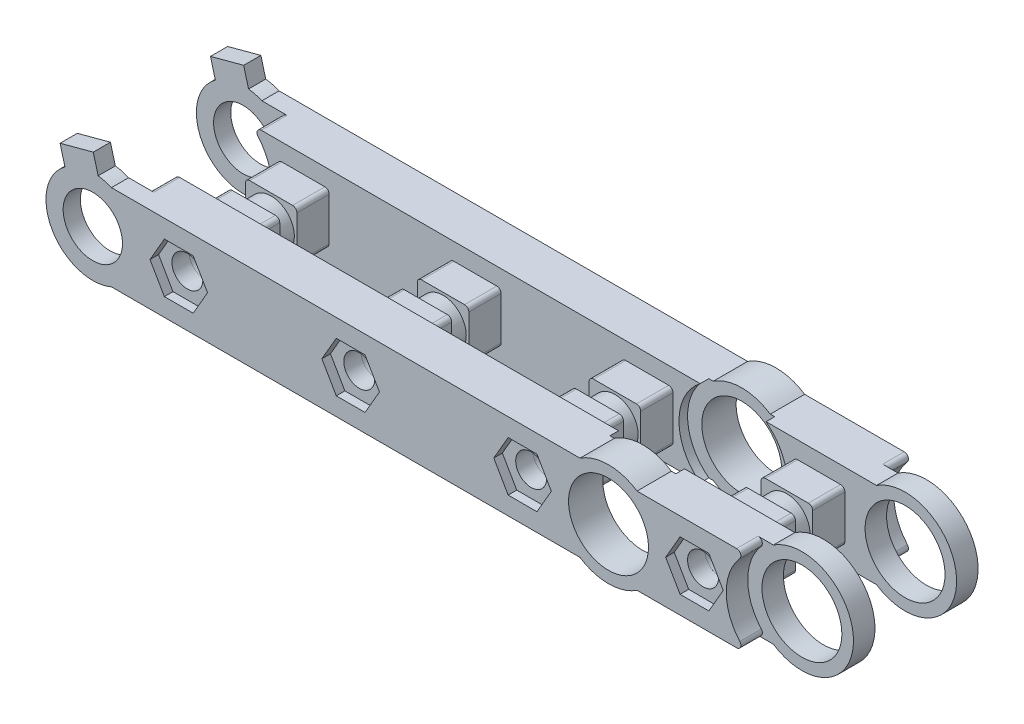
SolidWorks part; units mm, degrees
material "ABS"
ref_plane "正面" through (0, 0, 0) normal (0, 0, 1) x (1, 0, 0)
ref_plane "平面" through (0, 0, 0) normal (0, 1, 0) x (1, 0, 0)
ref_plane "右側面" through (0, 0, 0) normal (1, 0, 0) x (0, 0, -1)
sketch "ｽｹｯﾁ1" plane through (0, 0, 0) normal (0, 0, 1) x (1, 0, 0)
  line L0 (0, 0) -> (-20, 0) construction
  line L1 (3.64, -3.64) -> (-3.64, -3.64) construction
  line L2 (3.64, -3.64) -> (3.64, 3.64) construction
  line L3 (3.64, 3.64) -> (-3.64, 3.64) construction
  line L4 (-3.64, -3.64) -> (-3.64, 3.64) construction
  line L5 (3.64, -3.64) -> (-3.64, 3.64) construction
  line L6 (3.64, 3.64) -> (-3.64, -3.64) construction
  line L7 (-20, 0) -> (-40, 0) construction
  line L8 (-40, 0) -> (-60, 0) construction
  line L9 (-60, 0) -> (-80, 0) construction
  line L10 (-80, 0) -> (-100, 0) construction
  line L11 (0, 5) -> (-20, 5) construction
  line L18 (-20, 5) -> (-40, 5) construction
  line L19 (-40, 5) -> (-60, 5) construction
  line L20 (-60, 5) -> (-77.8315, 5) construction
  line L21 (-80, 5) -> (-100, 5) construction
  line L22 (0, -5) -> (-20, -5) construction
  line L23 (-20, -5) -> (-40, -5) construction
  line L24 (-40, -5) -> (-60, -5) construction
  line L25 (-60, -5) -> (-77.8315, -5) construction
  line L26 (-80, -5) -> (-100, -5) construction
  line L27 (-102.1685, 5) -> (-80, 5) construction
  line L28 (-77.8315, 5) -> (-60, 5)
  line L29 (-60, 5) -> (-40, 5)
  line L30 (-40, 5) -> (-20, 5)
  line L31 (-20, 5) -> (-3.3166, 5)
  line L32 (-3.3166, -5) -> (-20, -5)
  line L33 (-20, -5) -> (-40, -5)
  line L34 (-40, -5) -> (-60, -5)
  line L35 (-60, -5) -> (-77.8315, -5)
  line L36 (-80, -5) -> (-102.1685, -5) construction
  line L39 (-60, 5) -> (-80, 5) construction
  line L40 (-60, -5) -> (-80, -5) construction
  line L41 (-80, 5) -> (-77.8315, 5) construction
  line L42 (-80, -5) -> (-77.8315, -5) construction
  circle A0 centre (-10, 0) radius 1.8
  circle A1 centre (-30, 0) radius 1.8
  circle A2 centre (-50, 0) radius 1.8
  circle A3 centre (-70, 0) radius 1.8
  circle A4 centre (-90, 0) radius 1.8 construction
  circle A5 centre (-100, 0) radius 3.45 construction
  arc A6 (-3.3166, -5) -> (-3.3166, 5) centre (0, 0) ccw
  arc A7 (-102.1685, 5) -> (-102.1685, -5) centre (-100, 0) ccw construction
  circle A8 centre (0, 0) radius 4.39
  circle A9 centre (-80, 0) radius 3.45
  arc A11 (-77.8315, 5) -> (-77.8315, -5) centre (-80, 0) ccw
  point P0 (0, 0)
  dimension "D8" = 3.6
  dimension "D9" = 6.9
  dimension "D10" = 12
  dimension "D13" = 10.9
  dimension "D3" = 8.78
  dimension "D4" = 6.9
  dimension "D5" = 10.9
  dimension "D1" = 7.28
  dimension "D2" = 7.28
  dimension "D7" = 20
  dimension "D11" = 5
  dimension "D12" = 5
extrude "ﾎﾞｽ - 押し出し1" add sketch "ｽｹｯﾁ1" along normal blind 2
sketch "ｽｹｯﾁ2" plane through (0, 0, 0) normal (0, 0, -1) x (-1, 0, 0)
  line L19 (77.8315, 5) -> (60, 5)
  line L20 (60, 5) -> (40, 5)
  line L21 (40, 5) -> (20, 5)
  line L22 (20, 5) -> (3.3166, 5)
  line L23 (3.3166, -5) -> (20, -5)
  line L24 (20, -5) -> (40, -5)
  line L25 (40, -5) -> (60, -5)
  line L26 (60, -5) -> (77.8315, -5)
  line L29 (74.902, 5) -> (60, 5)
  line L30 (60, 5) -> (40, 5)
  line L31 (40, 5) -> (20, 5)
  line L32 (20, 5) -> (3.3166, 5)
  line L33 (3.3166, -5) -> (20, -5)
  line L34 (20, -5) -> (40, -5)
  line L35 (40, -5) -> (60, -5)
  line L36 (60, -5) -> (74.902, -5)
  circle A1 centre (30, 0) radius 1.8
  circle A2 centre (30, 0) radius 1.8
  circle A3 centre (10, 0) radius 1.8
  circle A4 centre (10, 0) radius 1.8
  arc A7 (75.2768, 4.1691) -> (75.2768, -4.1691) centre (80, 0) ccw
  circle A9 centre (70, 0) radius 1.8
  circle A10 centre (70, 0) radius 1.8
  circle A11 centre (50, 0) radius 1.8
  circle A12 centre (50, 0) radius 1.8
  arc A14 (3.3166, 5) -> (3.3166, -5) centre (0, 0) ccw
  arc A16 (3.3166, 5) -> (3.3166, -5) centre (0, 0) ccw
  circle A18 centre (0, 0) radius 4.39 construction
  circle A19 centre (0, 0) radius 4.39
  arc A20 (75.2768, -4.1691) -> (74.902, -5) centre (74.902, -4.5) cw
  arc A21 (75.2768, 4.1691) -> (74.902, 5) centre (74.902, 4.5) ccw
  arc A22 (77.8315, -5) -> (77.8315, 5) centre (80, 0) ccw
  dimension "D4" = 0.5
  dimension "D3" = 6.3
  dimension "D1" = 0
  dimension "D2" = 0
  dimension "D6" = 0
  dimension "D7" = 0
  dimension "D8" = 0
extrude "ﾎﾞｽ - 押し出し2" add sketch "ｽｹｯﾁ2" along normal blind 3
ref_plane "平面1" through (0, 0, -17.5) normal (0, 0, 1) x (1, 0, 0)
ref_plane "平面2" through (0, 0, -7.75) normal (0, 0, 1) x (1, 0, 0)
sketch "ｽｹｯﾁ3" plane through (0, 0, 2) normal (0, 0, 1) x (1, 0, 0)
  line L0 (-80, 0) -> (-80, 5.45) construction
  line L2 (-80, 0) -> (-81.4106, 5.2643) construction
  line L3 (-79.9446, 7.5206) -> (-79.0128, 4.0433)
  line L4 (-79.9446, 7.5206) -> (-83.8083, 6.4853)
  line L5 (-79.0128, 4.0433) -> (-82.8765, 3.008)
  line L6 (-83.8083, 6.4853) -> (-82.8765, 3.008)
  line L7 (-79.9446, 7.5206) -> (-82.8765, 3.008) construction
  line L8 (-79.0128, 4.0433) -> (-83.8083, 6.4853) construction
  arc A1 (-77.8315, 5) -> (-77.8315, -5) centre (-80, 0) ccw construction
  dimension "D1" = 1.8
  dimension "D2" = 4
  dimension "D3" = 15
extrude "ﾎﾞｽ - 押し出し3" add sketch "ｽｹｯﾁ3" against normal up to surface (2 mm away) up to face at (-76.55, 0, 0)
sketch "ｽｹｯﾁ4" plane through (0, 0, -17.5) normal (0, 0, 1) x (1, 0, 0)
  line L19 (-60, 5) -> (-77.8315, 5)
  line L20 (-40, 5) -> (-60, 5)
  line L21 (-20, 5) -> (-40, 5)
  line L22 (-3.3166, 5) -> (-20, 5)
  line L23 (-20, -5) -> (-3.3166, -5)
  line L24 (-40, -5) -> (-20, -5)
  line L25 (-60, -5) -> (-40, -5)
  line L26 (-77.8315, -5) -> (-60, -5)
  line L29 (-60, 5) -> (-77.8315, 5)
  line L30 (-40, 5) -> (-60, 5)
  line L31 (-20, 5) -> (-40, 5)
  line L32 (-3.3166, 5) -> (-20, 5)
  line L33 (-20, -5) -> (-3.3166, -5)
  line L34 (-40, -5) -> (-20, -5)
  line L35 (-60, -5) -> (-40, -5)
  line L36 (-77.8315, -5) -> (-60, -5)
  circle A0 centre (0, 0) radius 4.39 construction
  circle A1 centre (-30, 0) radius 1.8
  circle A2 centre (-30, 0) radius 1.8
  circle A3 centre (-10, 0) radius 1.8
  circle A4 centre (-10, 0) radius 1.8
  circle A5 centre (-80, 0) radius 3.45 construction
  circle A7 centre (-80, 0) radius 3.45
  circle A9 centre (-70, 0) radius 1.8
  circle A10 centre (-70, 0) radius 1.8
  circle A11 centre (-50, 0) radius 1.8
  circle A12 centre (-50, 0) radius 1.8
  circle A13 centre (0, 0) radius 4.39
  arc A14 (-3.3166, -5) -> (-3.3166, 5) centre (0, 0) ccw
  arc A15 (-77.8315, 5) -> (-77.8315, -5) centre (-80, 0) ccw
  arc A16 (-3.3166, -5) -> (-3.3166, 5) centre (0, 0) ccw
  arc A21 (-77.8315, 5) -> (-77.8315, -5) centre (-80, 0) ccw
  dimension "D1" = 0
  dimension "D2" = 0
  dimension "D6" = 0
  dimension "D7" = 0
  dimension "D8" = 0
extrude "ﾎﾞｽ - 押し出し4" add sketch "ｽｹｯﾁ4" along normal blind 2 separate body
sketch "ｽｹｯﾁ5" plane through (0, 0, -15.5) normal (0, 0, 1) x (1, 0, 0)
  line L18 (-74.902, -5) -> (-60, -5)
  line L19 (-60, -5) -> (-40, -5)
  line L20 (-40, -5) -> (-20, -5)
  line L21 (-20, -5) -> (-3.3166, -5)
  line L22 (-3.3166, 5) -> (-20, 5)
  line L23 (-20, 5) -> (-40, 5)
  line L24 (-40, 5) -> (-60, 5)
  line L25 (-60, 5) -> (-74.902, 5)
  line L28 (-74.902, -5) -> (-60, -5)
  line L29 (-60, -5) -> (-40, -5)
  line L30 (-40, -5) -> (-20, -5)
  line L31 (-20, -5) -> (-3.3166, -5)
  line L32 (-3.3166, 5) -> (-20, 5)
  line L33 (-20, 5) -> (-40, 5)
  line L34 (-40, 5) -> (-60, 5)
  line L35 (-60, 5) -> (-74.902, 5)
  circle A0 centre (0, 0) radius 4.39 construction
  circle A1 centre (-10, 0) radius 1.8
  circle A2 centre (-10, 0) radius 1.8
  circle A3 centre (-30, 0) radius 1.8
  circle A4 centre (-30, 0) radius 1.8
  circle A5 centre (-50, 0) radius 1.8
  circle A6 centre (-50, 0) radius 1.8
  circle A7 centre (-70, 0) radius 1.8
  circle A8 centre (-70, 0) radius 1.8
  circle A11 centre (0, 0) radius 4.39
  arc A12 (-3.3166, -5) -> (-3.3166, 5) centre (0, 0) ccw
  arc A14 (-3.3166, -5) -> (-3.3166, 5) centre (0, 0) ccw
  arc A20 (-75.2768, -4.1691) -> (-74.902, -5) centre (-74.902, -4.5) ccw
  arc A22 (-75.2768, -4.1691) -> (-74.902, -5) centre (-74.902, -4.5) ccw
  arc A23 (-75.2768, -4.1691) -> (-75.2768, 4.1691) centre (-80, 0) ccw
  arc A24 (-75.2768, -4.1691) -> (-75.2768, 4.1691) centre (-80, 0) ccw
  arc A25 (-74.902, 5) -> (-75.2768, 4.1691) centre (-74.902, 4.5) ccw
  arc A26 (-74.902, 5) -> (-75.2768, 4.1691) centre (-74.902, 4.5) ccw
  dimension "D1" = 0
  dimension "D2" = 0
  dimension "D4" = 0
  dimension "D5" = 0
  dimension "D7" = 0
extrude "ﾎﾞｽ - 押し出し5" add sketch "ｽｹｯﾁ5" along normal blind 3
sketch "ｽｹｯﾁ12" plane through (0, 0, 2) normal (0, 0, 1) x (1, 0, 0)
  circle A0 centre (0, 0) radius 6.3
  dimension "D1" = 12.6
extrude "ｶｯﾄ - 押し出し5" cut sketch "ｽｹｯﾁ12" against normal blind 2.5
sketch "ｽｹｯﾁ14" plane through (0, 0, -3) normal (0, 0, -1) x (-1, 0, 0)
  circle A1 centre (0, 0) radius 6.3
  circle A2 centre (0, 0) radius 6.3
  dimension "D1" = 0
extrude "ｶｯﾄ - 押し出し7" cut sketch "ｽｹｯﾁ14" against normal blind 1
fillet "ﾌｨﾚｯﾄ1" radius 0.5 4 edges at (-3.8328, -5, 0.75) (-3.8328, -5, -2.5) (-3.8328, 5, -2.5) (-3.8328, 5, 0.75)
sketch "ｽｹｯﾁ15" plane through (0, 0, -17.5) normal (0, 0, -1) x (-1, 0, 0)
  circle A1 centre (0, 0) radius 6.3
  circle A2 centre (0, 0) radius 6.3
  dimension "D1" = 0
extrude "ｶｯﾄ - 押し出し8" cut sketch "ｽｹｯﾁ15" against normal blind 2.5
sketch "ｽｹｯﾁ16" plane through (0, 0, -12.5) normal (0, 0, 1) x (1, 0, 0)
  circle A1 centre (0, 0) radius 6.3
  circle A2 centre (0, 0) radius 6.3
  dimension "D1" = 0
extrude "ｶｯﾄ - 押し出し9" cut sketch "ｽｹｯﾁ16" against normal blind 1
fillet "ﾌｨﾚｯﾄ2" radius 0.5 4 edges at (-3.8328, -5, -16.25) (-3.8328, -5, -13) (-3.8328, 5, -16.25) (-3.8328, 5, -13)
sketch "ｽｹｯﾁ6" plane through (0, 0, -17.5) normal (0, 0, -1) x (-1, 0, 0)
  line L4 (79.9446, 7.5206) -> (79.0128, 4.0433)
  line L5 (79.0128, 4.0433) -> (82.8765, 3.008)
  line L6 (82.8765, 3.008) -> (83.8083, 6.4853)
  line L7 (83.8083, 6.4853) -> (79.9446, 7.5206)
  line L8 (79.9446, 7.5206) -> (79.0128, 4.0433)
  line L9 (79.0128, 4.0433) -> (82.8765, 3.008)
  line L10 (82.8765, 3.008) -> (83.8083, 6.4853)
  line L11 (83.8083, 6.4853) -> (79.9446, 7.5206)
  dimension "D1" = 0
extrude "ﾎﾞｽ - 押し出し6" add sketch "ｽｹｯﾁ6" against normal up to surface (2 mm away) up to face at (-77.0998, 0, -15.5)
sketch "ｽｹｯﾁ7" plane through (0, 0, -3) normal (0, 0, -1) x (-1, 0, 0)
  line L0 (26.9, -3.1) -> (26.9, 3.1)
  line L1 (6.9, -3.1) -> (13.1, -3.1)
  line L2 (6.9, -3.1) -> (6.9, 3.1)
  line L3 (6.9, 3.1) -> (13.1, 3.1)
  line L4 (13.1, -3.1) -> (13.1, 3.1)
  line L5 (6.9, -3.1) -> (13.1, 3.1) construction
  line L6 (6.9, 3.1) -> (13.1, -3.1) construction
  line L7 (26.9, -3.1) -> (33.1, -3.1)
  line L8 (26.9, 3.1) -> (33.1, 3.1)
  line L9 (33.1, -3.1) -> (33.1, 3.1)
  line L10 (26.9, -3.1) -> (33.1, 3.1) construction
  line L11 (26.9, 3.1) -> (33.1, -3.1) construction
  line L12 (46.9, -3.1) -> (46.9, 3.1)
  line L13 (46.9, -3.1) -> (53.1, -3.1)
  line L14 (46.9, 3.1) -> (53.1, 3.1)
  line L15 (53.1, -3.1) -> (53.1, 3.1)
  line L16 (46.9, -3.1) -> (53.1, 3.1) construction
  line L17 (46.9, 3.1) -> (53.1, -3.1) construction
  line L18 (66.9, -3.1) -> (66.9, 3.1)
  line L19 (66.9, -3.1) -> (73.1, -3.1)
  line L20 (66.9, 3.1) -> (73.1, 3.1)
  line L21 (73.1, -3.1) -> (73.1, 3.1)
  line L22 (66.9, -3.1) -> (73.1, 3.1) construction
  line L23 (66.9, 3.1) -> (73.1, -3.1) construction
  line L30 (5.098, 5) -> (77.8315, 5) construction
  line L31 (5.098, 5) -> (77.8315, 5) construction
  line L32 (5.098, 5) -> (77.8315, 5) construction
  circle A0 centre (30, 0) radius 1.8 construction
  circle A1 centre (50, 0) radius 1.8 construction
  circle A2 centre (70, 0) radius 1.8 construction
  point P0 (10, 0)
  point P7 (30, 0)
  point P8 (50, 0)
  point P9 (70, 0)
  dimension "D1" = 6.2
  dimension "D2" = 6.2
extrude "ｶｯﾄ - 押し出し1" cut sketch "ｽｹｯﾁ7" against normal blind 2
sketch "ｽｹｯﾁ8" plane through (0, 0, -12.5) normal (0, 0, 1) x (1, 0, 0)
  line L0 (-13, -3) -> (-7, -3)
  line L1 (-7, -3) -> (-7, 3)
  line L2 (-7, 3) -> (-13, 3)
  line L3 (-13, 3) -> (-13, -3)
  line L4 (-13.1, -3.1) -> (-6.9, -3.1)
  line L5 (-13.1, 3.1) -> (-13.1, -3.1)
  line L6 (-6.9, 3.1) -> (-13.1, 3.1)
  line L7 (-6.9, -3.1) -> (-6.9, 3.1)
  line L8 (-13.1, -3.1) -> (-6.9, -3.1) construction
  line L9 (-13.1, 3.1) -> (-13.1, -3.1) construction
  line L10 (-6.9, 3.1) -> (-13.1, 3.1) construction
  line L11 (-6.9, -3.1) -> (-6.9, 3.1) construction
  line L12 (-26.9, -3.1) -> (-26.9, 3.1)
  line L13 (-26.9, 3.1) -> (-33.1, 3.1)
  line L14 (-33.1, 3.1) -> (-33.1, -3.1)
  line L15 (-33.1, -3.1) -> (-26.9, -3.1)
  line L16 (-26.9, -3.1) -> (-26.9, 3.1) construction
  line L17 (-26.9, 3.1) -> (-33.1, 3.1) construction
  line L18 (-33.1, 3.1) -> (-33.1, -3.1) construction
  line L19 (-33.1, -3.1) -> (-26.9, -3.1) construction
  line L28 (-66.9, -3.1) -> (-66.9, 3.1)
  line L29 (-66.9, 3.1) -> (-73.1, 3.1)
  line L30 (-73.1, 3.1) -> (-73.1, -3.1)
  line L31 (-73.1, -3.1) -> (-66.9, -3.1)
  line L32 (-66.9, -3.1) -> (-66.9, 3.1) construction
  line L33 (-66.9, 3.1) -> (-73.1, 3.1) construction
  line L34 (-73.1, 3.1) -> (-73.1, -3.1) construction
  line L35 (-73.1, -3.1) -> (-66.9, -3.1) construction
  line L36 (-46.9, -3.1) -> (-46.9, 3.1)
  line L37 (-53.1, -3.1) -> (-46.9, -3.1)
  line L38 (-53.1, 3.1) -> (-53.1, -3.1)
  line L39 (-46.9, 3.1) -> (-53.1, 3.1)
  line L40 (-46.9, -3.1) -> (-46.9, 3.1) construction
  line L41 (-53.1, -3.1) -> (-46.9, -3.1) construction
  line L42 (-53.1, 3.1) -> (-53.1, -3.1) construction
  line L43 (-46.9, 3.1) -> (-53.1, 3.1) construction
  line L44 (-27, -3) -> (-27, 3)
  line L45 (-27, 3) -> (-33, 3)
  line L46 (-33, 3) -> (-33, -3)
  line L47 (-33, -3) -> (-27, -3)
  line L52 (-67, -3) -> (-67, 3)
  line L53 (-67, 3) -> (-73, 3)
  line L54 (-73, 3) -> (-73, -3)
  line L55 (-73, -3) -> (-67, -3)
  line L56 (-47, -3) -> (-47, 3)
  line L57 (-47, 3) -> (-53, 3)
  line L58 (-53, 3) -> (-53, -3)
  line L59 (-53, -3) -> (-47, -3)
  circle A1 centre (-70, 0) radius 1.8 construction
  circle A2 centre (-50, 0) radius 1.8 construction
  circle A3 centre (-30, 0) radius 1.8 construction
  circle A4 centre (-10, 0) radius 1.8 construction
  circle A6 centre (-70, 0) radius 1.8
  circle A7 centre (-50, 0) radius 1.8
  circle A8 centre (-30, 0) radius 1.8
  circle A9 centre (-10, 0) radius 1.8
  dimension "D1" = 0
  dimension "D2" = 0
  dimension "D4" = 0
  dimension "D5" = 0
  dimension "D6" = 0.1
extrude "ﾎﾞｽ - 押し出し7" add sketch "ｽｹｯﾁ8" along normal up to surface (11.5 mm away) up to face at (-8.2, 0, -1)
sketch "ｽｹｯﾁ9" plane through (0, 0, -7.75) normal (0, 0, 1) x (1, 0, 0)
  line L12 (-27, -3) -> (-27, 3)
  line L13 (-27, 3) -> (-33, 3)
  line L14 (-33, 3) -> (-33, -3)
  line L15 (-33, -3) -> (-27, -3)
  line L16 (-27, -3) -> (-27, 3)
  line L17 (-27, 3) -> (-33, 3)
  line L18 (-33, 3) -> (-33, -3)
  line L19 (-33, -3) -> (-27, -3)
  line L20 (-13, -3) -> (-7, -3)
  line L21 (-7, -3) -> (-7, 3)
  line L22 (-7, 3) -> (-13, 3)
  line L23 (-13, 3) -> (-13, -3)
  line L24 (-13, -3) -> (-7, -3)
  line L25 (-7, -3) -> (-7, 3)
  line L26 (-7, 3) -> (-13, 3)
  line L27 (-13, 3) -> (-13, -3)
  line L28 (-47, -3) -> (-47, 3)
  line L29 (-47, 3) -> (-53, 3)
  line L30 (-53, 3) -> (-53, -3)
  line L31 (-53, -3) -> (-47, -3)
  line L32 (-47, -3) -> (-47, 3)
  line L33 (-47, 3) -> (-53, 3)
  line L34 (-53, 3) -> (-53, -3)
  line L35 (-53, -3) -> (-47, -3)
  line L36 (-67, -3) -> (-67, 3)
  line L37 (-67, 3) -> (-73, 3)
  line L38 (-73, 3) -> (-73, -3)
  line L39 (-73, -3) -> (-67, -3)
  line L40 (-67, -3) -> (-67, 3)
  line L41 (-67, 3) -> (-73, 3)
  line L42 (-73, 3) -> (-73, -3)
  line L43 (-73, -3) -> (-67, -3)
  circle A1 centre (-70, 0) radius 2.7
  circle A3 centre (-50, 0) radius 2.7
  circle A5 centre (-30, 0) radius 2.7
  circle A7 centre (-10, 0) radius 2.7
  dimension "D6" = 5.4
  dimension "D2" = 0
  dimension "D3" = 0
  dimension "D4" = 0
  dimension "D5" = 0
extrude "ｶｯﾄ - 押し出し2" cut sketch "ｽｹｯﾁ9" against normal blind 1 and the other way blind 1
sketch "ｽｹｯﾁ10" plane through (0, 0, 2) normal (0, 0, 1) x (1, 0, 0)
  line L1 (-11.6743, 2.9) -> (-13.3486, 0)
  line L2 (-13.3486, 0) -> (-11.6743, -2.9)
  line L3 (-11.6743, -2.9) -> (-8.3257, -2.9)
  line L4 (-8.3257, -2.9) -> (-6.6514, 0)
  line L5 (-6.6514, 0) -> (-8.3257, 2.9)
  line L6 (-8.3257, 2.9) -> (-11.6743, 2.9)
  line L33 (-31.6743, -2.9) -> (-28.3257, -2.9)
  line L34 (-28.3257, -2.9) -> (-26.6514, 0)
  line L35 (-26.6514, 0) -> (-28.3257, 2.9)
  line L36 (-28.3257, 2.9) -> (-31.6743, 2.9)
  line L37 (-31.6743, 2.9) -> (-33.3486, 0)
  line L38 (-33.3486, 0) -> (-31.6743, -2.9)
  line L39 (-51.6743, -2.9) -> (-48.3257, -2.9)
  line L40 (-48.3257, -2.9) -> (-46.6514, 0)
  line L41 (-46.6514, 0) -> (-48.3257, 2.9)
  line L42 (-48.3257, 2.9) -> (-51.6743, 2.9)
  line L43 (-51.6743, 2.9) -> (-53.3486, 0)
  line L44 (-53.3486, 0) -> (-51.6743, -2.9)
  line L45 (-68.3257, -2.9) -> (-66.6514, 0)
  line L46 (-66.6514, 0) -> (-68.3257, 2.9)
  line L47 (-68.3257, 2.9) -> (-71.6743, 2.9)
  line L48 (-71.6743, 2.9) -> (-73.3486, 0)
  line L49 (-73.3486, 0) -> (-71.6743, -2.9)
  line L50 (-71.6743, -2.9) -> (-68.3257, -2.9)
  circle A0 centre (-10, 0) radius 2.9 construction
  circle A1 centre (-30, 0) radius 2.9 construction
  circle A2 centre (-50, 0) radius 2.9 construction
  circle A3 centre (-70, 0) radius 2.9 construction
  dimension "D1" = 5.8
extrude "ｶｯﾄ - 押し出し3" cut sketch "ｽｹｯﾁ10" against normal blind 1
sketch "ｽｹｯﾁ11" plane through (0, 0, -17.5) normal (0, 0, -1) x (-1, 0, 0)
  circle A0 centre (10, 0) radius 3.25
  circle A1 centre (30, 0) radius 3.25
  circle A2 centre (50, 0) radius 3.25
  circle A3 centre (70, 0) radius 3.25
  dimension "D1" = 6.5
extrude "ｶｯﾄ - 押し出し4" cut sketch "ｽｹｯﾁ11" against normal blind 1.5
sketch "ｽｹｯﾁ17" plane through (0, 0, 2) normal (0, 0, 1) x (1, 0, 0)
  line L0 (-30, 0) -> (-10, 0) construction
  circle A0 centre (-20, 0) radius 4.65
  dimension "D1" = 9.3
extrude "ｶｯﾄ - 押し出し10" cut sketch "ｽｹｯﾁ17" against normal through all
sketch "ｽｹｯﾁ18" plane through (0, 0, -3) normal (0, 0, -1) x (-1, 0, 0)
  circle A0 centre (20, 0) radius 6.3
  dimension "D1" = 12.6
extrude "ｶｯﾄ - 押し出し11" cut sketch "ｽｹｯﾁ18" against normal blind 1
sketch "ｽｹｯﾁ19" plane through (0, 0, -12.5) normal (0, 0, 1) x (1, 0, 0)
  circle A1 centre (-20, 0) radius 6.3
  circle A2 centre (-20, 0) radius 6.3
  dimension "D1" = 0
extrude "ｶｯﾄ - 押し出し12" cut sketch "ｽｹｯﾁ19" against normal blind 1
sketch "ｽｹｯﾁ20" plane through (0, 0, -13.5) normal (0, 0, 1) x (1, 0, 0)
  line L0 (-23.3166, 5) -> (-16.6834, 5)
  line L1 (-5.098, 5) -> (-77.8315, 5) construction
  line L2 (-23.3166, -5) -> (-16.6834, -5)
  line L3 (-77.8315, -5) -> (-5.098, -5) construction
  arc A0 (-23.3166, -5) -> (-16.6834, -5) centre (-20, 0) ccw
  arc A1 (-16.6834, 5) -> (-23.3166, 5) centre (-20, 0) ccw
  dimension "D1" = 12
extrude "ﾎﾞｽ - 押し出し8" add sketch "ｽｹｯﾁ20" against normal up to surface (4 mm away) up to face at (-15.35, 0, -17.5)
sketch "ｽｹｯﾁ21" plane through (0, 0, -2) normal (0, 0, -1) x (-1, 0, 0)
  line L1 (23.3166, -5) -> (16.6834, -5)
  line L2 (23.3166, -5) -> (16.6834, -5)
  line L3 (16.6834, 5) -> (23.3166, 5)
  line L4 (16.6834, 5) -> (23.3166, 5)
  arc A1 (16.6834, -5) -> (23.3166, -5) centre (20, 0) ccw
  arc A2 (16.6834, -5) -> (23.3166, -5) centre (20, 0) ccw
  arc A3 (23.3166, 5) -> (16.6834, 5) centre (20, 0) ccw
  arc A4 (23.3166, 5) -> (16.6834, 5) centre (20, 0) ccw
  dimension "D1" = 0
  dimension "D2" = 0
extrude "ﾎﾞｽ - 押し出し9" add sketch "ｽｹｯﾁ21" against normal up to surface (4 mm away) up to face at (-15.35, 0, 2)
sketch "ｽｹｯﾁ22" plane through (0, 0, -2) normal (0, 0, -1) x (-1, 0, 0)
  line L2 (5.098, 5) -> (3.3166, 5)
  line L3 (3.3166, -5) -> (5.098, -5)
  line L4 (5.098, 5) -> (3.3166, 5)
  line L5 (3.3166, -5) -> (5.098, -5)
  circle A0 centre (0, 0) radius 4.39 construction
  circle A1 centre (0, 0) radius 4.39
  arc A4 (3.3166, 5) -> (3.3166, -5) centre (0, 0) ccw
  arc A5 (4.7232, -4.1691) -> (5.098, -5) centre (5.098, -4.5) ccw
  arc A6 (4.7232, -4.1691) -> (4.7232, 4.1691) centre (0, 0) ccw
  arc A7 (5.098, 5) -> (4.7232, 4.1691) centre (5.098, 4.5) ccw
  arc A8 (3.3166, 5) -> (3.3166, -5) centre (0, 0) ccw
  arc A9 (4.7232, -4.1691) -> (5.098, -5) centre (5.098, -4.5) ccw
  arc A10 (4.7232, -4.1691) -> (4.7232, 4.1691) centre (0, 0) ccw
  arc A11 (5.098, 5) -> (4.7232, 4.1691) centre (5.098, 4.5) ccw
  dimension "D1" = 0
extrude "ﾎﾞｽ - 押し出し10" add sketch "ｽｹｯﾁ22" along normal up to surface (1 mm away) up to face at (-10, 0, -3)
sketch "ｽｹｯﾁ23" plane through (0, 0, -13.5) normal (0, 0, 1) x (1, 0, 0)
  line L2 (-3.3166, 5) -> (-5.098, 5)
  line L3 (-5.098, -5) -> (-3.3166, -5)
  line L4 (-3.3166, 5) -> (-5.098, 5)
  line L5 (-5.098, -5) -> (-3.3166, -5)
  circle A1 centre (0, 0) radius 4.39
  circle A2 centre (0, 0) radius 4.39
  arc A6 (-3.3166, -5) -> (-3.3166, 5) centre (0, 0) ccw
  arc A7 (-5.098, -5) -> (-4.7232, -4.1691) centre (-5.098, -4.5) ccw
  arc A8 (-4.7232, 4.1691) -> (-4.7232, -4.1691) centre (0, 0) ccw
  arc A9 (-4.7232, 4.1691) -> (-5.098, 5) centre (-5.098, 4.5) ccw
  arc A10 (-3.3166, -5) -> (-3.3166, 5) centre (0, 0) ccw
  arc A11 (-5.098, -5) -> (-4.7232, -4.1691) centre (-5.098, -4.5) ccw
  arc A12 (-4.7232, 4.1691) -> (-4.7232, -4.1691) centre (0, 0) ccw
  arc A13 (-4.7232, 4.1691) -> (-5.098, 5) centre (-5.098, 4.5) ccw
  dimension "D1" = 0
  dimension "D2" = 0
extrude "ﾎﾞｽ - 押し出し11" add sketch "ｽｹｯﾁ23" along normal up to surface (1 mm away) up to face at (-8.425, 0, -12.5)
fillet "ﾌｨﾚｯﾄ3" radius 0.5 32 edges at (-13, -3, -3.875) (-13, -3, -10.625) (-7, -3, -10.625) (-7, -3, -3.875) (-7, 3, -3.875) (-7, 3, -10.625) (-13, 3, -10.625) (-13, 3, -3.875) (-27, -3, -3.875) (-27, -3, -10.625) (-27, 3, -3.875) (-27, 3, -10.625) (-33, -3, -3.875) (-33, -3, -10.625) (-33, 3, -10.625) (-33, 3, -3.875) (-53, -3, -3.875) (-53, -3, -10.625) (-47, -3, -3.875) (-47, -3, -10.625) (-47, 3, -3.875) (-47, 3, -10.625) (-53, 3, -10.625) (-53, 3, -3.875) (-67, -3, -3.875) (-67, -3, -10.625) (-67, 3, -10.625) (-67, 3, -3.875) (-73, -3, -3.875) (-73, -3, -10.625) (-73, 3, -10.625) (-73, 3, -3.875)
sketch "ｽｹｯﾁ24" plane through (0, 0, -0.5) normal (0, 0, 1) x (1, 0, 0)
  circle A0 centre (0, 0) radius 4.65
  dimension "D1" = 9.3
extrude "ｶｯﾄ - 押し出し13" cut sketch "ｽｹｯﾁ24" against normal through all
